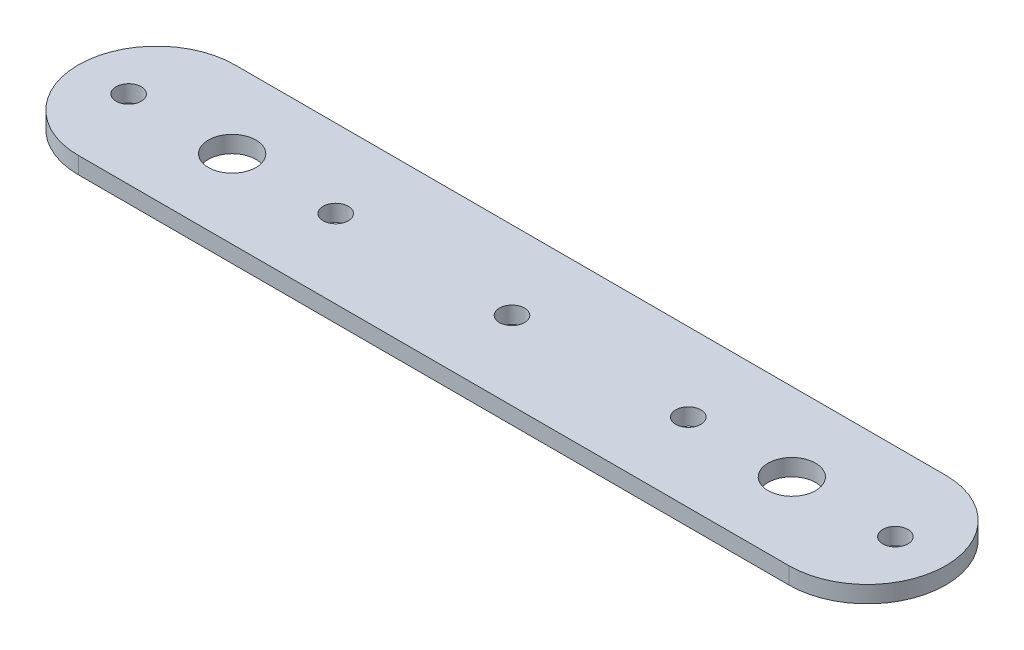
SolidWorks part; units mm, degrees
ref_plane "前视" through (0, 0, 0) normal (0, 0, 1) x (1, 0, 0)
ref_plane "上视" through (0, 0, 0) normal (0, 1, 0) x (1, 0, 0)
ref_plane "右视" through (0, 0, 0) normal (1, 0, 0) x (0, 0, -1)
sketch "草图1" plane through (0, 0, 0) normal (0, 1, 0) x (1, 0, 0)
  line L1 (-77.5, 14) -> (77.5, 14)
  line L2 (-77.5, 14) -> (-77.5, -14)
  line L3 (-77.5, -14) -> (77.5, -14)
  line L4 (77.5, 14) -> (77.5, -14)
  line L5 (-77.5, 14) -> (77.5, -14) construction
  line L6 (-77.5, -14) -> (77.5, 14) construction
  point P0 (0, 0)
  dimension "D1" = 155
  dimension "D2" = 28
extrude "凸台-拉伸1" add sketch "草图1" along normal blind 3 contours L2 | L2 | L3 L1 | L4 | L4 region at (0, 0, 0)
sketch "草图2" plane through (0, 3, 0) normal (0, 1, 0) x (1, 0, 0)
  circle A0 centre (-50, 0) radius 4.25
  circle A1 centre (50, 0) radius 4.25
  circle A2 centre (0, 0) radius 2.25
  dimension "D1" = 8.5
  dimension "D2" = 8.5
  dimension "D5" = 4.5
  dimension "D3" = 100
  dimension "D4" = 50
extrude "切除-拉伸1" cut sketch "草图2" against normal up to next
fillet "圆角1" 2 edges at (-77.5, 1.5, 14) (-77.5, 1.5, -14) type full round first side face at (0, 1.5, 14) second side face at (0, 1.5, -14) middle face at (-77.5, 1.5, 0)
sketch "草图3" plane through (0, 3, 0) normal (0, 1, 0) x (1, 0, 0)
  circle A0 centre (-68.5, 0) radius 2.25
  circle A1 centre (-31.5, 0) radius 2.25
  circle A2 centre (31.5, 0) radius 2.25
  circle A3 centre (68.5, 0) radius 2.25
  circle A4 centre (-50, 0) radius 4.25 construction
  circle A5 centre (50, 0) radius 4.25 construction
  dimension "D2" = 18.5
  dimension "D3" = 4.5
  dimension "D4" = 4.5
  dimension "D6" = 18.5
  dimension "D7" = 4.5
  dimension "D8" = 4.5
  dimension "D1" = 37
  dimension "D5" = 37
extrude "切除-拉伸2" cut sketch "草图3" against normal up to next
fillet "圆角2" 2 edges at (77.5, 1.5, 14) (77.5, 1.5, -14) type full round first side face at (7, 1.5, 14) second side face at (7, 1.5, -14) middle face at (77.5, 1.5, 0)
